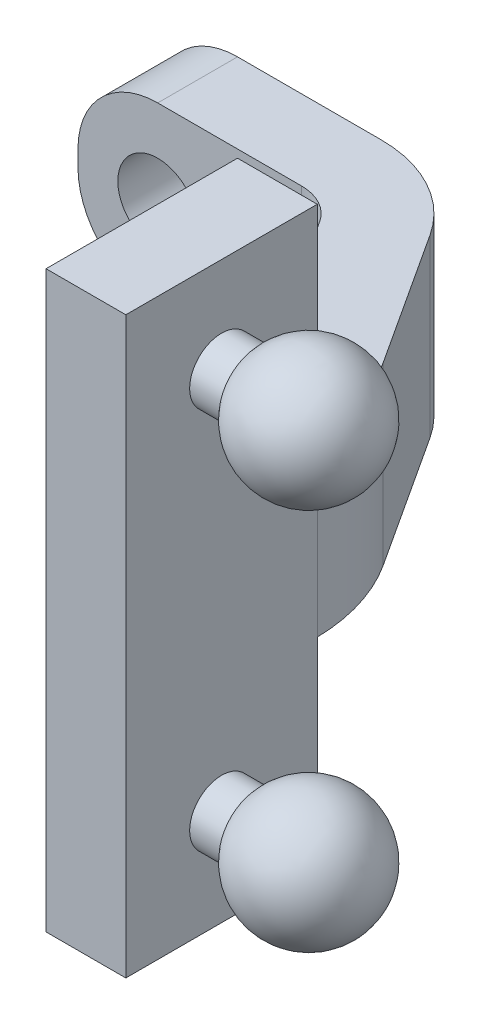
SolidWorks part; units mm, degrees
ref_plane "前视基准面" through (0, 0, 0) normal (0, 0, 1) x (1, 0, 0)
ref_plane "上视基准面" through (0, 0, 0) normal (0, 1, 0) x (1, 0, 0)
ref_plane "右视基准面" through (0, 0, 0) normal (1, 0, 0) x (0, 0, -1)
other "Configuration Table"
sketch "草图1" plane through (0, 0, 0) normal (0, 1, 0) x (1, 0, 0)
  line L0 (0, 0) -> (7, 0)
  line L1 (14, -9.1042) -> (14, -15)
  line L2 (0, -2.5) -> (7, -2.5)
  line L3 (11.5, -9.1042) -> (11.5, -15)
  line L4 (11.5, -15) -> (14, -15)
  line L5 (0, 0) -> (0, -2.5)
  line L6 (10.3535, -1.8196) -> (13.0862, -6.0224)
  line L7 (8.2575, -3.1823) -> (10.9903, -7.3852)
  arc A0 (7, 0) -> (10.3535, -1.8196) centre (7, -4) cw
  arc A3 (7, -2.5) -> (8.2575, -3.1823) centre (7, -4) cw
  arc A6 (9.6623, -0.4928) -> (14, -9.1042) centre (3.2834, -9.1042) cw construction
  arc A7 (10.3535, -1.8196) -> (9.6623, -0.4928) centre (16.8788, 2.4233) ccw construction
  arc A8 (8.2575, -3.1823) -> (7.6722, -2.1578) centre (16.8788, 2.4233) ccw construction
  arc A9 (7.6722, -2.1578) -> (11.5, -9.1042) centre (3.2834, -9.1042) cw construction
  arc A10 (13.0862, -6.0224) -> (14, -9.1042) centre (8.3466, -9.1042) cw
  arc A11 (11.5, -9.1042) -> (10.9903, -7.3852) centre (8.3466, -9.1042) ccw
  dimension "D1" = 2.5
  dimension "D3" = 4
  dimension "D4" = 14
  dimension "D2" = 7
  dimension "D6" = 15
extrude "凸台-拉伸1" add sketch "草图1" along normal mid plane 5.5
sketch "草图2" plane through (0, 0, 0) normal (0, 0, -1) x (-1, 0, 0)
  line L0 (0, 2.75) -> (0, -2.75) construction
  circle A0 centre (-2.5, 0) radius 1.25
  point P5 (0, 0)
  dimension "D1" = 2.5
  dimension "D2" = 2.5
extrude "切除-拉伸1" cut sketch "草图2" against normal blind 10
fillet "圆角2" radius 2.5 2 edges at (0, -2.75, 1.25) (0, 2.75, 1.25)
sketch "草图4" plane through (11.5, 0, 0) normal (-1, 0, 0) x (0, 0, 1)
  line L0 (15, 2.75) -> (15, -2.75) construction
  line L1 (9, 9) -> (15, 9)
  line L2 (9, 9) -> (9, -9)
  line L3 (9, -9) -> (15, -9)
  line L4 (15, 9) -> (15, -9)
  line L5 (9, 9) -> (15, -9) construction
  line L6 (9, -9) -> (15, 9) construction
  point P0 (12, 0)
  dimension "D1" = 18
  dimension "D2" = 6
extrude "凸台-拉伸2" add sketch "草图4" against normal up to surface (2.5 mm away) up to face at (14, 0, 12.0521)
sketch "草图5" plane through (14, 0, 0) normal (1, 0, 0) x (0, 0, -1)
  line L0 (-9, 9) -> (-15, 9) construction
  line L1 (-9, -9) -> (-9, 9) construction
  circle A0 centre (-12, 6) radius 1
  dimension "D1" = 2
  dimension "D2" = 3
  dimension "D3" = 3
extrude "凸台-拉伸3" add sketch "草图5" along normal blind 1
ref_axis "基准轴1" through (15, 6, 12) along (-1, 0, 0)
ref_plane "基准面1" through (0, 0, 12) normal (0, 0, -1) x (-1, 0, 0)
sketch "草图6" plane through (0, 0, 12) normal (0, 0, -1) x (-1, 0, 0)
  line L0 (-15, 6) -> (-18.7321, 6)
  line L1 (-15, 7) -> (-15, 5) construction
  line L2 (-15, 6) -> (-14, 6) construction
  line L3 (-15, 6) -> (-15, 7)
  line L4 (-14, 7) -> (-15, 7) construction
  arc A0 (-15, 7) -> (-18.7321, 6) centre (-16.7321, 6) ccw
  dimension "D1" = 4
revolve "旋转1" add sketch "草图6" angle 360 about L0
mirror "镜向1" about plane through (0, 0, 0) normal (0, 1, 0) of "凸台-拉伸3", "旋转1"
